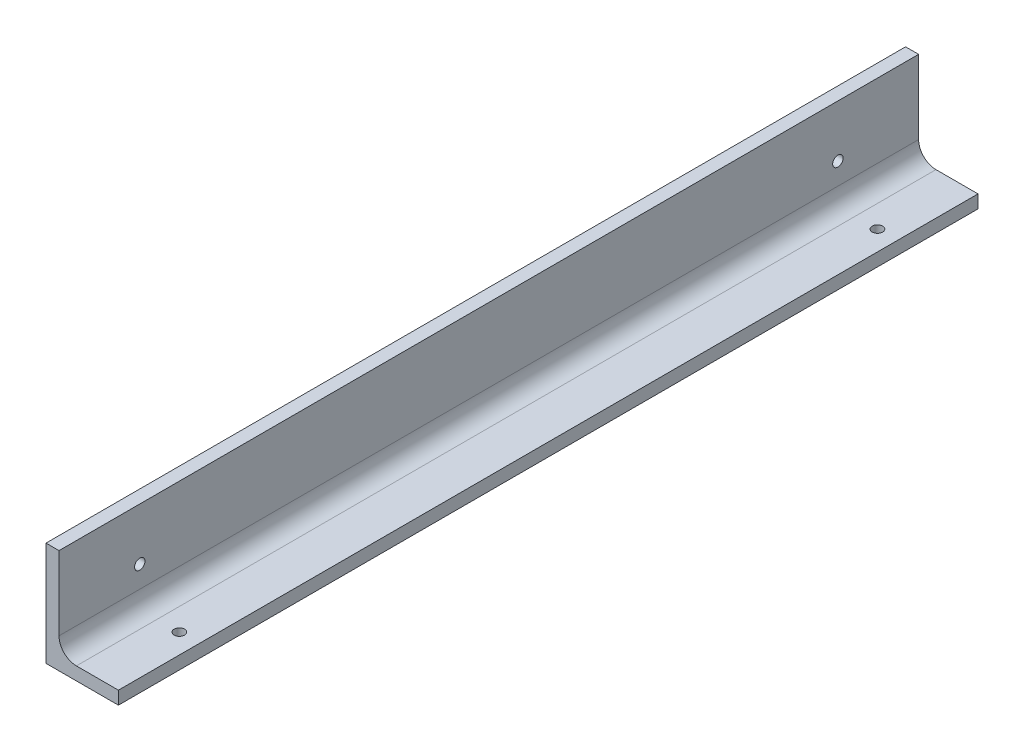
SolidWorks part; units mm, degrees
ref_plane "Front Plane" through (0, 0, 0) normal (0, 0, 1) x (1, 0, 0)
ref_plane "Top Plane" through (0, 0, 0) normal (0, 1, 0) x (1, 0, 0)
ref_plane "Right Plane" through (0, 0, 0) normal (1, 0, 0) x (0, 0, -1)
sketch "Sketch1" plane through (0, 0, 0) normal (0, 0, 1) x (1, 0, 0)
  line L0 (0, 50.8) -> (0, 0)
  line L1 (0, 0) -> (0, 170.18) construction
  line L2 (0, 0) -> (35.306, 0)
  line L3 (35.306, 0) -> (35.306, 6.35)
  line L4 (35.306, 6.35) -> (14.8176, 6.35)
  line L5 (0, 50.8) -> (6.35, 50.8)
  line L6 (6.35, 50.8) -> (6.35, 14.8176)
  arc A0 (6.35, 14.8176) -> (14.8176, 6.35) centre (14.8176, 14.8176) ccw
  dimension "D1" = 50.8
  dimension "D2" = 35.306
  dimension "D3" = 6.35
extrude "Boss-Extrude1" add sketch "Sketch1" against normal up to surface (419.1 mm away)
sketch "Sketch2" plane through (6.35, 0, 0) normal (1, 0, 0) x (0, 0, -1)
  line L0 (209.55, 50.8) -> (209.55, 14.8176) construction
  line L1 (419.1, 50.8) -> (0, 50.8) construction
  line L2 (419.1, 14.8176) -> (0, 14.8176) construction
  line L3 (39.37, 50.8) -> (39.37, 25.4) construction
  line L4 (39.37, 25.4) -> (39.37, 14.8176) construction
  circle A0 centre (39.37, 25.4) radius 2.54
  circle A1 centre (379.73, 25.4) radius 2.54
  dimension "D1" = 5.08
extrude "Cut-Extrude1" cut sketch "Sketch2" against normal through all
sketch "Sketch3" plane through (0, 6.35, 0) normal (0, 1, 0) x (1, 0, 0)
  line L0 (35.306, 209.55) -> (0, 209.55) construction
  line L1 (35.306, 419.1) -> (35.306, 0) construction
  line L2 (0, 419.1) -> (0, 0) construction
  line L10 (35.306, 39.37) -> (25.654, 39.37) construction
  line L11 (25.654, 39.37) -> (14.8176, 39.37) construction
  line L12 (14.8176, 419.1) -> (14.8176, 0) construction
  circle A0 centre (25.654, 39.37) radius 2.54
  circle A1 centre (25.654, 379.73) radius 2.54
  dimension "D2" = 5.08
  dimension "D1" = 9.652
extrude "Cut-Extrude2" cut sketch "Sketch3" against normal through all
